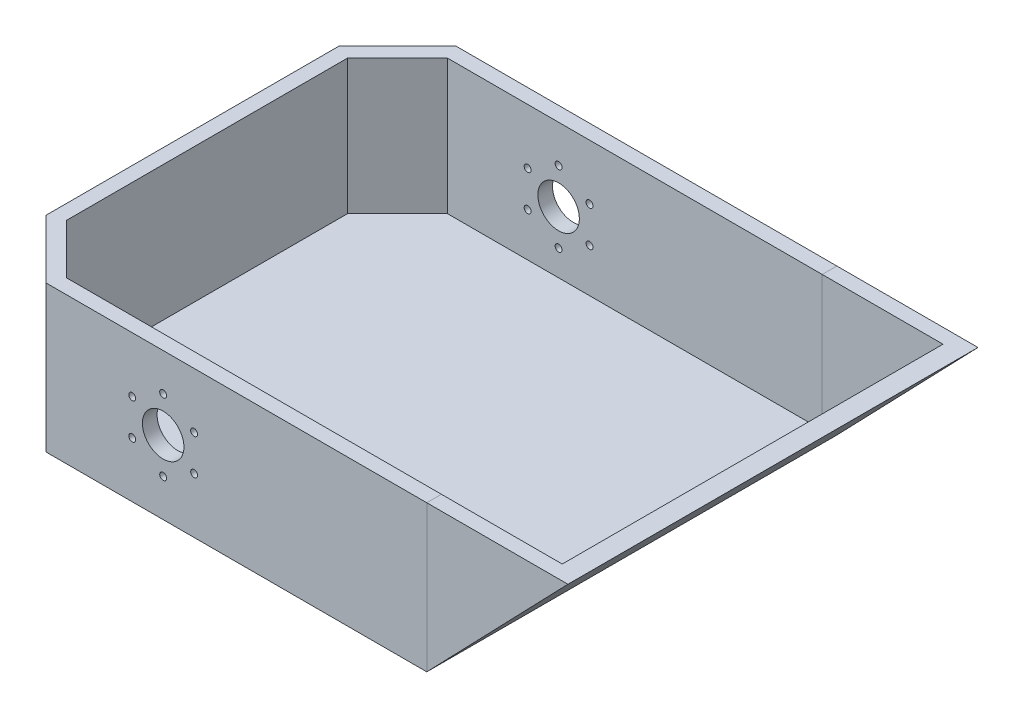
SolidWorks part; units mm, degrees
ref_plane "Front Plane" through (0, 0, 0) normal (0, 0, 1) x (1, 0, 0)
ref_plane "Top Plane" through (0, 0, 0) normal (0, 1, 0) x (1, 0, 0)
ref_plane "Right Plane" through (0, 0, 0) normal (1, 0, 0) x (0, 0, -1)
sketch "Sketch2" plane through (0, 0, 0) normal (0, 1, 0) x (1, 0, 0)
  line L1 (-127, 76.2) -> (63.5, 76.2)
  line L2 (-127, 76.2) -> (-127, -101.6)
  line L3 (-127, -101.6) -> (63.5, -101.6)
  line L4 (63.5, 76.2) -> (63.5, -101.6)
  dimension "D1" = 190.5
  dimension "D2" = 177.8
  dimension "D3" = 76.2
  dimension "D4" = 63.5
extrude "Boss-Extrude1" add sketch "Sketch2" along normal blind 5.08
chamfer "Chamfer1" distance 25.4 angle 45 2 edges at (-127, 2.54, -76.2) (-127, 2.54, 101.6)
sketch "Sketch4" plane through (0, 5.08, 0) normal (0, 1, 0) x (1, 0, 0)
  line L0 (57.15, 69.85) -> (-98.9697, 69.85)
  line L1 (-98.9697, 69.85) -> (-120.65, 48.1697)
  line L2 (-120.65, 48.1697) -> (-120.65, -73.5697)
  line L3 (-120.65, -73.5697) -> (-98.9697, -95.25)
  line L4 (-98.9697, -95.25) -> (57.15, -95.25)
  line L6 (63.5, 76.2) -> (-101.6, 76.2)
  line L7 (-101.6, 76.2) -> (-127, 50.8)
  line L8 (-127, 50.8) -> (-127, -76.2)
  line L9 (-127, -76.2) -> (-101.6, -101.6)
  line L10 (-101.6, -101.6) -> (63.5, -101.6)
  line L11 (63.5, -101.6) -> (63.5, 76.2)
  line L12 (63.5, 76.2) -> (-101.6, 76.2)
  line L13 (-101.6, 76.2) -> (-127, 50.8)
  line L14 (-127, 50.8) -> (-127, -76.2)
  line L15 (-127, -76.2) -> (-101.6, -101.6)
  line L16 (-101.6, -101.6) -> (63.5, -101.6)
  line L17 (63.5, -101.6) -> (63.5, -95.25)
  line L18 (57.15, 69.85) -> (63.5, 69.85)
  line L19 (57.15, -95.25) -> (63.5, -95.25)
  line L20 (63.5, 69.85) -> (63.5, 76.2)
  line L21 (63.5, -101.6) -> (63.5, 76.2) construction
  line L22 (57.15, -95.25) -> (57.15, 69.85) construction
  dimension "D2" = 6.35
  dimension "D1" = 0
extrude "Boss-Extrude3" add sketch "Sketch4" along normal blind 58.42
sketch "Sketch5" plane through (0, 0, 101.6) normal (0, 0, 1) x (1, 0, 0)
  line L0 (-150.3871, 38.1) -> (157.7429, 38.1) construction
  line L1 (-101.6, 0) -> (63.5, 0) construction
  line L2 (0, -14.9262) -> (0, 83.7522) construction
  line L3 (-50.8, 49.8289) -> (-50.8, 11.4994) construction
  line L5 (-71.0506, 31.75) -> (-33.7726, 31.75) construction
  circle A0 centre (-50.8, 31.75) radius 9
  circle A1 centre (-50.8, 31.75) radius 15.5 construction
  circle A2 centre (-50.8, 47.25) radius 1.5
  circle A3 centre (-37.3766, 39.5) radius 1.5
  circle A4 centre (-37.3766, 24) radius 1.5
  circle A5 centre (-50.8, 16.25) radius 1.5
  circle A6 centre (-64.2234, 24) radius 1.5
  circle A7 centre (-64.2234, 39.5) radius 1.5
  dimension "D2" = 18
  dimension "D5" = 31
  dimension "D6" = 3
  dimension "D1" = 38.1
  dimension "D3" = 50.8
  dimension "D4" = 6.35
  dimension "D7" = 6
extrude "Cut-Extrude1" cut sketch "Sketch5" against normal through all
sketch "Sketch8" plane through (0, 0, 101.6) normal (0, 0, 1) x (1, 0, 0)
  line L0 (63.5, 0) -> (63.5, 63.5)
  line L1 (63.5, 63.5) -> (124.6993, 63.5)
  line L2 (124.6993, 63.5) -> (63.5, 0)
extrude "Boss-Extrude4" add sketch "Sketch8" along direction (0, 0, 1) on the side against the normal up to surface (177.8 mm away) separate body up to face at (-62.7234, 39.5, -76.2)
sketch "Sketch9" plane through (0, 63.5, 0) normal (0, 1, 0) x (1, 0, 0)
  line L0 (63.5, 69.85) -> (118.3493, 69.85)
  line L1 (118.3493, 69.85) -> (118.3493, -95.25)
  line L2 (118.3493, -95.25) -> (63.5, -95.25)
  line L3 (63.5, 69.85) -> (63.5, -95.25)
  line L4 (124.6993, 76.2) -> (124.6993, -101.6) construction
  line L5 (124.6993, -101.6) -> (63.5, -101.6) construction
  dimension "D1" = 6.35
  dimension "D2" = 6.35
extrude "Cut-Extrude3" cut sketch "Sketch9" against normal offset from surface (2.9285 mm away) 6.35 up to face at (94.0997, 31.75, 12.7)
